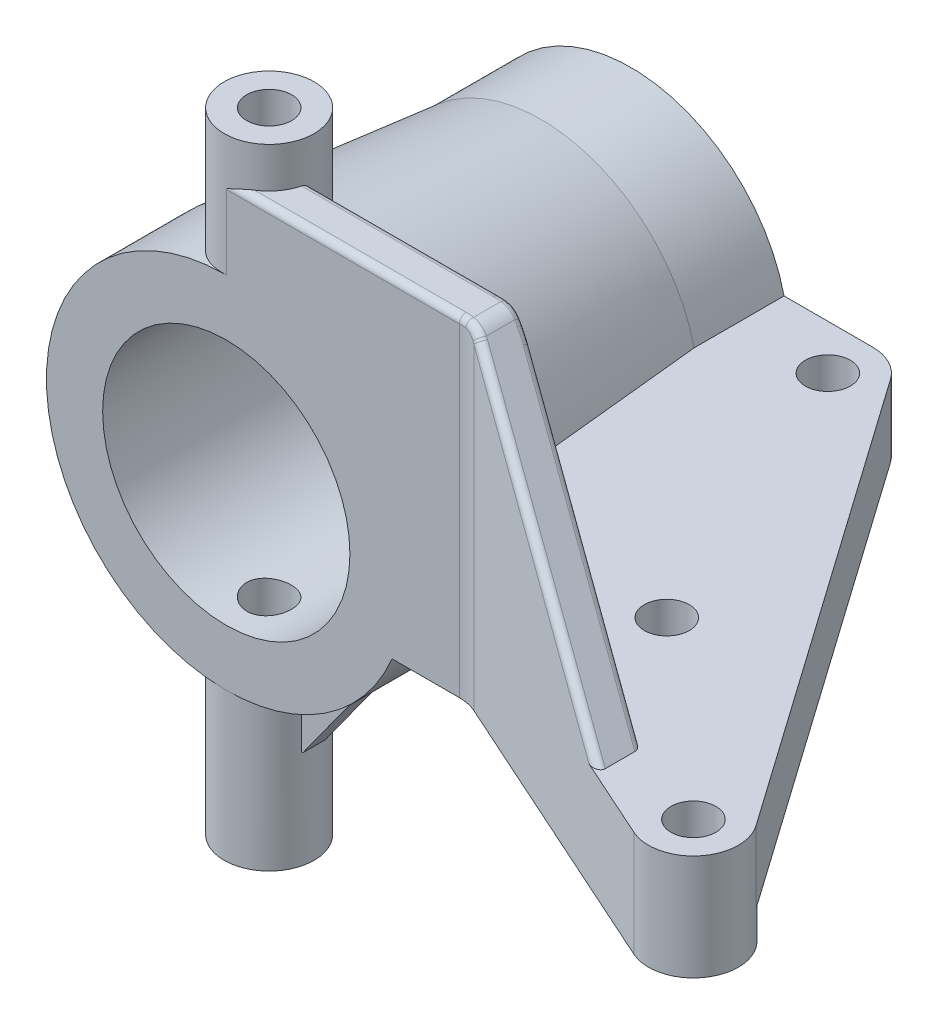
SolidWorks part; units mm, degrees
ref_plane "Front Plane" through (0, 0, 0) normal (0, 0, 1) x (1, 0, 0)
ref_plane "Top Plane" through (0, 0, 0) normal (0, 1, 0) x (1, 0, 0)
ref_plane "Right Plane" through (0, 0, 0) normal (1, 0, 0) x (0, 0, -1)
sketch "Sketch1" plane through (0, 0, 0) normal (0, 1, 0) x (1, 0, 0)
  line L0 (0, 0) -> (0, 22.86)
  line L1 (0, 22.86) -> (5.0315, 22.86)
  line L2 (7.1088, 21.7818) -> (25.1437, -3.8468)
  line L3 (22.0241, -7.6249) -> (5.5772, -0.2237)
  line L4 (0, 0) -> (4.5348, 0)
  arc A0 (25.1437, -3.8468) -> (22.0241, -7.6249) centre (23.0665, -5.3086) cw
  arc A1 (5.0315, 22.86) -> (7.1088, 21.7818) centre (5.0315, 20.32) cw
  arc A2 (5.5772, -0.2237) -> (4.5348, 0) centre (4.5348, -2.54) ccw
  circle A3 centre (23.0665, -5.3086) radius 1.27
  circle A4 centre (5.0315, 20.32) radius 1.27
  circle A5 centre (12.4437, 3.81) radius 1.27
  point P13 (30.48, -11.43)
  point P16 (6.35, 22.86)
  point P19 (5.08, 0)
  dimension "D6" = 2.54
  dimension "D7" = 2.54
  dimension "D8" = 2.54
  dimension "D9" = 2.54
  dimension "D10" = 2.54
  dimension "D11" = 2.54
  dimension "D1" = 6.35
  dimension "D2" = 22.86
  dimension "D3" = 5.08
  dimension "D4" = 34.29
  dimension "D5" = 30.48
  dimension "D12" = 19.05
  dimension "D13" = 12.7
extrude "Boss-Extrude1" add sketch "Sketch1" along normal mid plane 4.064
sketch "Sketch2" plane through (0, 2.032, 0) normal (0, 1, 0) x (1, 0, 0)
  line L0 (18.0967, -5.8575) -> (5.5772, -0.2237)
  line L1 (5.5772, -0.2237) -> (22.0241, -7.6249) construction
  line L2 (4.5348, 0) -> (-8.636, 0)
  line L3 (18.0967, -3.3507) -> (18.0967, -5.8575)
  line L4 (18.0967, -3.3507) -> (6.5152, 1.8609)
  line L5 (6.5152, 1.8609) -> (5.5772, -0.2237) construction
  line L6 (4.5348, 2.286) -> (-8.636, 2.286)
  line L7 (-8.636, 2.286) -> (-8.636, 0)
  line L8 (0, 22.86) -> (0, 0) construction
  arc A0 (5.5772, -0.2237) -> (4.5348, 0) centre (4.5348, -2.54) ccw
  arc A1 (4.5348, 2.286) -> (6.5152, 1.8609) centre (4.5348, -2.54) cw
  line M6 (0, 0) -> (4.5348, 0)
  arc M7 (4.5348, 0) -> (5.5772, -0.2237) centre (4.5348, -2.54) cw
  line M8 (5.5772, -0.2237) -> (22.0241, -7.6249)
  line M13 (0, 22.86) -> (0, 0)
  dimension "D1" = 2.286
  dimension "D2" = 12.7
  dimension "D3" = 2.286
  dimension "D4" = 8.636
extrude "Boss-Extrude2" add sketch "Sketch2" along normal blind 12.7 contours L4 L5 L3 M8 | L5 A1 L6 M13 M6 M7 | L6 L7 L2 M13 region at (12.0684, 2.032, 1.9076) region at (3.0494, 2.032, -1.1445) region at (-4.318, 2.032, -1.143)
sketch "Sketch3" plane through (0, 0, -2.286) normal (0, 0, -1) x (-1, 0, 0)
  line L0 (-18.0967, 2.032) -> (-5.525, 14.732)
  line L1 (-4.5348, 14.732) -> (-6.5152, 14.732) construction
  line L2 (-18.0967, 2.032) -> (-18.0967, 14.732)
  line L3 (-18.0967, 14.732) -> (-5.525, 14.732)
extrude "Cut-Extrude1" cut sketch "Sketch3" against normal through all
sketch "Sketch4" plane through (0, 0, 0) normal (0, 1, 0) x (1, 0, 0)
  line L0 (-8.636, 22.86) -> (-8.636, 0) construction
  line L1 (-8.636, 0) -> (4.5348, 0) construction
  line L2 (0.254, 22.86) -> (0.254, 17.78)
  line L4 (0.254, 17.78) -> (1.524, 5.08)
  line L5 (1.524, 5.08) -> (1.524, 0)
  line L6 (0.254, 22.86) -> (-4.826, 22.86)
  line L7 (-4.826, 22.86) -> (-4.826, 0)
  line L8 (-4.826, 0) -> (1.524, 0)
  point P7 (-2.0506, 0)
  dimension "D1" = 8.636
  dimension "D2" = 10.16
  dimension "D3" = 5.08
  dimension "D4" = 5.08
  dimension "D5" = 7.62
  dimension "D6" = 0.254
revolve "Revolve1" add sketch "Sketch4" angle 360 about L0
sketch "Sketch8" plane through (0, 0, 0) normal (0, 1, 0) x (1, 0, 0)
  line L0 (-8.636, 0) -> (4.5348, 0) construction
  line L1 (-8.7537, 2.54) -> (-8.7537, 22.86) construction
  line L2 (0.0187, 22.86) -> (-17.526, 22.86) construction
  circle A0 centre (-8.7537, 2.54) radius 2.54
  dimension "D1" = 5.08
extrude "Boss-Extrude4" add sketch "Sketch8" along normal blind 17.018 and the other way blind 18.542
sketch "Sketch5" plane through (0, 0, -22.86) normal (0, 0, -1) x (-1, 0, 0)
  circle A0 centre (8.636, 0) radius 6.985
  dimension "D1" = 13.97
extrude "Cut-Extrude2" cut sketch "Sketch5" against normal through all
sketch "Sketch6" plane through (0, -2.032, 0) normal (0, -1, 0) x (1, 0, 0)
  line L0 (5.5772, 0.2237) -> (22.0241, 7.6249) construction
  line L1 (1.3187, 0) -> (4.5348, 0) construction
  line L3 (5.5772, 0.2237) -> (22.0241, 7.6249)
  line L4 (1.3187, 0) -> (4.5348, 0)
  line L5 (1.3187, -3.048) -> (0.508, -3.048)
  line L6 (20.202, 3.4625) -> (6.8279, -2.5558)
  line L7 (1.3187, -3.048) -> (4.5348, -3.048)
  line L8 (0.508, -3.048) -> (0.508, 0)
  line L9 (0.508, 0) -> (1.3187, 0)
  circle A0 centre (23.0665, 5.3086) radius 1.27
  arc A1 (21.5043, 3.3058) -> (22.0241, 7.6249) centre (23.0665, 5.3086) ccw
  circle A2 centre (23.0665, 5.3086) radius 1.27 construction
  arc A3 (25.1437, 3.8468) -> (22.0241, 7.6249) centre (23.0665, 5.3086) ccw construction
  arc A4 (4.5348, 0) -> (5.5772, 0.2237) centre (4.5348, 2.54) ccw construction
  arc A5 (4.5348, 0) -> (5.5772, 0.2237) centre (4.5348, 2.54) ccw
  arc A6 (4.5348, -3.048) -> (6.8279, -2.5558) centre (4.5348, 2.54) ccw
  arc A7 (20.202, 3.4625) -> (21.5043, 3.3058) centre (20.7232, 2.3044) cw
  dimension "D1" = 1.27
  dimension "D3" = 0.508
  dimension "D2" = 3.048
extrude "Boss-Extrude3" add sketch "Sketch6" along normal blind 1.905
ref_plane "Plane2" through (0, 0, -2.54) normal (0, 0, 1) x (1, 0, 0)
sketch "Sketch10" plane through (0, 0, -2.54) normal (0, 0, 1) x (1, 0, 0)
  line L0 (-6.2137, -12.954) -> (-2.9278, -8.4049)
  line L1 (-2.9278, -8.4049) -> (-6.8487, -8.4049)
  line L2 (-6.2137, -12.954) -> (-6.8487, -12.954)
  line L4 (-6.8487, -12.954) -> (-6.8487, -8.4049)
  line L5 (-6.2137, -18.542) -> (-6.2137, -9.867) construction
  arc A0 (-8.7537, -10.1593) -> (0.7302, -3.937) centre (-8.636, 0) ccw construction
  dimension "D1" = 4.5491
  dimension "D2" = 0.635
  dimension "D3" = 5.588
extrude "Boss-Extrude7" add sketch "Sketch10" along normal mid plane 1.27
fillet "Fillet1" radius 1.27 1 edges at (5.525, 14.732, -0.9912)
fillet "Fillet2" radius 0.381 10 edges at (-2.0506, 14.732, 0) (4.766, 14.732, 0.0105) (5.1926, 14.7166, 0.0866) (5.7467, 14.4858, 0.3) (-0.8458, 14.732, -2.286) (4.7653, 14.732, -2.2805) (5.4133, 14.6612, -2.2054) (6.2104, 14.0396, -1.9858) (11.9972, 8.1937, 3.1127) (12.3059, 7.8818, 0.7449)
sketch "Sketch11" plane through (0, 17.018, 0) normal (0, 1, 0) x (1, 0, 0)
  circle A0 centre (-8.7537, 2.54) radius 1.27
  circle A1 centre (-8.7537, 2.54) radius 2.54 construction
  dimension "D1" = 2.54
extrude "Cut-Extrude4" cut sketch "Sketch11" against normal through all
mirror "Mirror1" [suppressed] of bodies 110
sketch "Sketch12" [suppressed] plane through (0, 0, -22.86) normal (0, 0, -1) x (-1, 0, 0)
  line L0 (-16.1262, 32.004) -> (-16.1262, 2.032) construction
  line L1 (25.4, 17.018) -> (-31.75, 17.018)
  line L2 (25.4, 17.018) -> (25.4, -25.4)
  line L3 (25.4, -25.4) -> (-31.75, -25.4)
  line L4 (-31.75, 17.018) -> (-31.75, -25.4)
  line L5 (-25.1437, 32.004) -> (-7.1088, 32.004) construction
  line L6 (-25.1437, 2.032) -> (-7.1088, 2.032) construction
  point P11 (-16.1262, 17.018)
  dimension "D1" = 25.4
  dimension "D2" = 31.75
  dimension "D3" = 25.4
extrude "Cut-Extrude5" [suppressed] cut sketch "Sketch12" against normal through all
